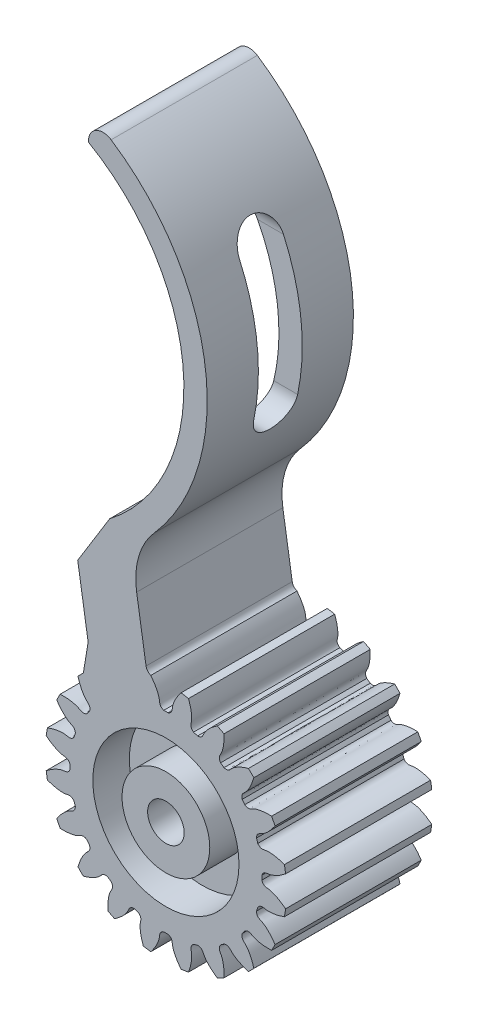
SolidWorks part; units mm, degrees
material "聚脂树脂"
ref_plane "前视基准面" through (0, 0, 0) normal (0, 0, 1) x (1, 0, 0)
ref_plane "上视基准面" through (0, 0, 0) normal (0, 1, 0) x (1, 0, 0)
ref_plane "右视基准面" through (0, 0, 0) normal (1, 0, 0) x (0, 0, -1)
other "Configuration Table"
sketch "草图1" plane through (0, 0, 0) normal (0, 0, 1) x (1, 0, 0)
  circle A0 centre (0, 0) radius 16.5
extrude "凸台-拉伸1" add sketch "草图1" along normal blind 20
ref_axis "基准轴1" through (0, 0, -1.5) along (0, 0, 1)
sketch "草图2" plane through (0, 0, 0) normal (0, 0, 1) x (1, 0, 0)
  line L0 (0, 0) -> (0, 16.5) construction
  circle A0 centre (0, 0) radius 16.5 construction
  arc A1 (0.29, 13.1218) -> (-0.29, 13.1218) centre (0, 0) ccw
  arc A2 (4.7717, 18.7474) -> (-4.7717, 18.7474) centre (0, 0) ccw
  spline S0 degree 3 poles (0.29, 13.1218) (0.9168, 13.3402) (0.8356, 13.7807) (0.9193, 14.205) (0.9283, 14.2463) (0.9395, 14.293) (0.9529, 14.3448) (0.969, 14.4018) (0.9878, 14.4638) (1.0095, 14.5309) (1.0345, 14.6028) (1.0629, 14.6795) (1.0948, 14.7608) (1.1305, 14.8467) (1.1702, 14.9371) (1.2141, 15.0317) (1.2623, 15.1305) (1.315, 15.2334) (1.3725, 15.3401) (1.4349, 15.4506) (1.5023, 15.5646) (1.575, 15.6821) (1.653, 15.8029) (1.7366, 15.9267) (1.826, 16.0534) (1.9211, 16.1829) (2.0223, 16.3149) (2.1296, 16.4493) (2.2432, 16.5859) (2.3632, 16.7244) (2.4897, 16.8646) (2.6229, 17.0065) (2.7628, 17.1496) (2.9095, 17.2939) (3.0632, 17.4391) (3.224, 17.585) (3.3918, 17.7313) (3.567, 17.8779) (3.7493, 18.0245) (3.9391, 18.1709) (4.1363, 18.3167) (4.4122, 18.5125) (4.6259, 18.6545) (4.7717, 18.7474) knots 0 0 0 0 0.165916 0.170906 0.176664 0.183189 0.190482 0.198542 0.207371 0.216967 0.22733 0.238462 0.250361 0.263027 0.276462 0.290664 0.305634 0.321371 0.337876 0.355149 0.37319 0.391998 0.411574 0.431917 0.453028 0.474907 0.497554 0.520968 0.54515 0.570099 0.595817 0.622302 0.649554 0.677575 0.706363 0.735918 0.766242 0.797333 0.829191 0.861818 0.895212 0.929373 1 1 1 1
  spline S1 degree 3 poles (-0.29, 13.1218) (-0.9168, 13.3402) (-0.8356, 13.7807) (-0.9193, 14.205) (-0.9283, 14.2463) (-0.9395, 14.293) (-0.9529, 14.3448) (-0.969, 14.4018) (-0.9878, 14.4638) (-1.0095, 14.5309) (-1.0345, 14.6028) (-1.0629, 14.6795) (-1.0948, 14.7608) (-1.1305, 14.8467) (-1.1702, 14.9371) (-1.2141, 15.0317) (-1.2623, 15.1305) (-1.315, 15.2334) (-1.3725, 15.3401) (-1.4349, 15.4506) (-1.5023, 15.5646) (-1.575, 15.6821) (-1.653, 15.8029) (-1.7366, 15.9267) (-1.826, 16.0534) (-1.9211, 16.1829) (-2.0223, 16.3149) (-2.1296, 16.4493) (-2.2432, 16.5859) (-2.3632, 16.7244) (-2.4897, 16.8646) (-2.6229, 17.0065) (-2.7628, 17.1496) (-2.9095, 17.2939) (-3.0632, 17.4391) (-3.224, 17.585) (-3.3918, 17.7313) (-3.567, 17.8779) (-3.7493, 18.0245) (-3.9391, 18.1709) (-4.1363, 18.3167) (-4.4122, 18.5125) (-4.6259, 18.6545) (-4.7717, 18.7474) knots 0 0 0 0 0.165916 0.170906 0.176664 0.183189 0.190482 0.198542 0.207371 0.216967 0.22733 0.238462 0.250361 0.263027 0.276462 0.290664 0.305634 0.321371 0.337876 0.355149 0.37319 0.391998 0.411574 0.431917 0.453028 0.474907 0.497554 0.520968 0.54515 0.570099 0.595817 0.622302 0.649554 0.677575 0.706363 0.735918 0.766242 0.797333 0.829191 0.861818 0.895212 0.929373 1 1 1 1
extrude "切除-拉伸1" cut sketch "草图2" along normal through all
pattern_circular "阵列(圆周)1" count 20 over 360 about axis through (0, 0, -1.5) along (0, 0, 1) of "切除-拉伸1"
sketch "草图3" plane through (0, 0, 0) normal (0, 0, 1) x (1, 0, 0)
  circle A0 centre (0, 0) radius 15 construction
  dimension "Dn" = 30
sketch "草图4" plane through (0, 0, 20) normal (0, 0, 1) x (1, 0, 0)
  line L0 (0, 0) -> (0, 24.252) construction
  line L1 (0, 0) -> (-4.1504, 26.2048) construction
  line L2 (-14.6667, -3.2847) -> (-22.6322, 47.0071) construction
  line L3 (-12.7072, 29.0903) -> (-7.9015, -1.2515)
  line L4 (-4.8057, 30.3418) -> (0, 0)
  line L5 (-11.2693, 79.2123) -> (-10.5853, 75.2708)
  line L6 (-11.294, 12.029) -> (-10.6385, 16.029)
  line L7 (-3.0932, 16.2075) -> (-2.5812, 16.2969)
  line L8 (0, 0) -> (-34.8237, -5.5155) construction
  line L9 (-7.9015, -1.2515) -> (0, 0)
  circle A0 centre (0, 0) radius 12.5 construction
  circle A1 centre (-23.5381, 52.727) radius 29.189 construction
  arc A2 (-2.0665, 16.3701) -> (-3.0932, 16.2075) centre (0, 0) ccw construction
  arc A3 (-4.8057, 30.3418) -> (-11.2693, 79.2123) centre (-23.5381, 52.727) ccw
  circle A4 centre (-23.5381, 52.727) radius 26 construction
  arc A6 (-12.7072, 29.0903) -> (-10.5853, 75.2708) centre (-23.5381, 52.727) ccw
  arc A8 (-3.7791, 12.5692) -> (-4.3306, 12.39) centre (0, 0) ccw construction
  arc A9 (-7.024, 14.9303) -> (-7.9502, 14.4584) centre (0, 0) ccw construction
  arc A10 (-7.4782, 10.7862) -> (-7.9474, 10.4453) centre (0, 0) ccw construction
  arc A12 (-3.7791, 12.5692) -> (-4.3306, 12.39) centre (0, 0) ccw
  arc A13 (-7.024, 14.9303) -> (-7.9502, 14.4584) centre (0, 0) ccw
  arc A14 (-7.4782, 10.7862) -> (-7.9474, 10.4453) centre (0, 0) ccw
  spline S0 degree 3 poles (2295.3671, 1929.7263) (-117.6975, -134.774) (-40.8912, 20.8175) (-11.0168, 11.9483) (-10.7713, 11.8675) (-10.4966, 11.7648) (-10.2471, 11.6599) (-10.0224, 11.5547) (-9.822, 11.4509) (-9.671, 11.3649) (-9.5386, 11.2841) (-9.4441, 11.2225) (-9.3578, 11.1623) (-9.3008, 11.1209) (-9.2491, 11.0817) (-9.2026, 11.0451) (-9.1503, 11.0021) (-9.105, 10.9626) (-4.5559, 6.7443) (-24.7562, -23.4769) (1867.2073, 2351.7135) knots -12.160638 -12.160638 -12.160638 -12.160638 0.502446 0.525093 0.568083 0.608002 0.644851 0.678629 0.709336 0.736973 0.749639 0.77267 0.783033 0.792629 0.801458 0.809518 0.816811 0.829094 0.834084 3.350793 3.350793 3.350793 3.350793 only from (-11.294, 12.029) to (-7.9474, 10.4453) construction
  spline S1 degree 3 poles (-3000.2151, -128.3054) (33.5455, 6.2288) (-2.7783, 7.6499) (-3.5171, 13.8097) (-3.5224, 13.8696) (-3.5265, 13.9372) (-3.5289, 13.9963) (-3.5307, 14.0865) (-3.5293, 14.2134) (-3.5206, 14.3824) (-3.5033, 14.5733) (-3.4754, 14.7858) (-3.4352, 15.0192) (-3.381, 15.2729) (-3.3111, 15.5461) (-3.2398, 15.7847) (-3.1737, 15.9845) (7.1936, 45.3178) (178.2143, 16.0013) (-2910.3372, -722.7198) knots -2.350827 -2.350827 -2.350827 -2.350827 0.165916 0.170906 0.183189 0.190482 0.198542 0.207371 0.22733 0.250361 0.276462 0.305634 0.337876 0.37319 0.411574 0.453028 0.474907 0.497554 13.160601 13.160601 13.160601 13.160601 only from (-3.7791, 12.5692) to (-3.0932, 16.2075) construction
  spline S2 degree 3 poles (2779.3421, 1125.9713) (-153.5845, -91.8071) (-32.4569, 32.4347) (-6.7853, 14.7679) (-6.5768, 14.6152) (-6.3474, 14.4326) (-6.1425, 14.2557) (-5.9612, 14.0862) (-5.8028, 13.9257) (-5.6857, 13.7971) (-5.5848, 13.6794) (-5.514, 13.5916) (-5.4504, 13.5077) (-5.409, 13.4507) (-5.3719, 13.3975) (-5.3391, 13.3482) (-5.3027, 13.2912) (-5.2717, 13.2396) (-2.2488, 7.822) (-30.7993, -14.6778) (2502.5391, 1659.6136) knots -12.160638 -12.160638 -12.160638 -12.160638 0.502446 0.525093 0.568083 0.608002 0.644851 0.678629 0.709336 0.736973 0.749639 0.77267 0.783033 0.792629 0.801458 0.809518 0.816811 0.829094 0.834084 3.350793 3.350793 3.350793 3.350793 only from (-7.024, 14.9303) to (-4.3306, 12.39) construction
  spline S3 degree 3 poles (-2813.7256, -1049.1431) (29.9789, 16.29) (-5.0063, 6.4169) (-7.6124, 12.047) (-7.636, 12.1023) (-7.6607, 12.1653) (-7.6812, 12.2208) (-7.7108, 12.3061) (-7.7487, 12.4272) (-7.7927, 12.5905) (-7.8352, 12.7775) (-7.8743, 12.9882) (-7.9082, 13.2226) (-7.9351, 13.4806) (-7.9531, 13.762) (-7.959, 14.011) (-7.9578, 14.2215) (-7.1625, 45.3227) (164.5472, 70.2894) (-2544.5625, -1586.6911) knots -2.350827 -2.350827 -2.350827 -2.350827 0.165916 0.170906 0.183189 0.190482 0.198542 0.207371 0.22733 0.250361 0.276462 0.305634 0.337876 0.37319 0.411574 0.453028 0.474907 0.497554 13.160601 13.160601 13.160601 13.160601 only from (-7.4782, 10.7862) to (-7.9502, 14.4584) construction
  spline S4 degree 3 poles (-3.7791, 12.5692) (-3.2504, 12.9706) (-3.4637, 13.3644) (-3.5171, 13.8097) (-3.5224, 13.8696) (-3.5265, 13.9372) (-3.5289, 13.9963) (-3.5307, 14.0865) (-3.5293, 14.2134) (-3.5206, 14.3824) (-3.5033, 14.5733) (-3.4754, 14.7858) (-3.4352, 15.0192) (-3.381, 15.2729) (-3.3111, 15.5461) (-3.224, 15.8378) (-3.1479, 16.0599) (-3.1017, 16.1848) (-3.0932, 16.2075) knots 0 0 0 0 0.165916 0.170906 0.183189 0.190482 0.198542 0.207371 0.22733 0.250361 0.276462 0.305634 0.337876 0.37319 0.411574 0.453028 0.497554 0.507432 0.507432 0.507432 0.507432
  spline S5 degree 3 poles (-7.024, 14.9303) (-6.9129, 14.8568) (-6.7202, 14.7228) (-6.459, 14.5233) (-6.2419, 14.3433) (-6.0489, 14.1699) (-5.8792, 14.0047) (-5.7318, 13.8492) (-5.6234, 13.7255) (-5.5309, 13.613) (-5.4664, 13.5298) (-5.409, 13.4507) (-5.3719, 13.3975) (-5.3391, 13.3482) (-5.3027, 13.2912) (-5.2717, 13.2396) (-5.0532, 12.848) (-4.9943, 12.404) (-4.3306, 12.39) knots 0.492568 0.492568 0.492568 0.492568 0.546972 0.588426 0.62681 0.662124 0.694366 0.723538 0.749639 0.761538 0.783033 0.792629 0.801458 0.809518 0.816811 0.829094 0.834084 1 1 1 1
  spline S6 degree 3 poles (-7.4782, 10.7862) (-7.0995, 11.3313) (-7.424, 11.64) (-7.6124, 12.047) (-7.636, 12.1023) (-7.6607, 12.1653) (-7.6812, 12.2208) (-7.7108, 12.3061) (-7.7487, 12.4272) (-7.7927, 12.5905) (-7.8352, 12.7775) (-7.8743, 12.9882) (-7.9082, 13.2226) (-7.9351, 13.4806) (-7.9531, 13.762) (-7.9603, 14.0664) (-7.9566, 14.3011) (-7.9513, 14.4342) (-7.9502, 14.4584) knots 0 0 0 0 0.165916 0.170906 0.183189 0.190482 0.198542 0.207371 0.22733 0.250361 0.276462 0.305634 0.337876 0.37319 0.411574 0.453028 0.497554 0.507432 0.507432 0.507432 0.507432
  spline S7 degree 3 poles (-11.294, 12.029) (-11.1656, 11.9934) (-10.9409, 11.9255) (-10.6308, 11.8165) (-10.3687, 11.7125) (-10.1316, 11.6072) (-9.9192, 11.5025) (-9.7309, 11.4002) (-9.5896, 11.316) (-9.4669, 11.2376) (-9.3798, 11.1783) (-9.3008, 11.1209) (-9.2491, 11.0817) (-9.2026, 11.0451) (-9.1503, 11.0021) (-9.105, 10.9626) (-8.7761, 10.6576) (-8.5829, 10.2536) (-7.9474, 10.4453) knots 0.492568 0.492568 0.492568 0.492568 0.546972 0.588426 0.62681 0.662124 0.694366 0.723538 0.749639 0.761538 0.783033 0.792629 0.801458 0.809518 0.816811 0.829094 0.834084 1 1 1 1
  dimension "D6" = 52
  dimension "D7" = 76
  dimension "D5" = 30.72
  dimension "D10" = 25
  dimension "D9" = 80
  dimension "D1" = 9
  dimension "D2" = 15
  dimension "D3" = 8
  dimension "D4" = 30.72
  dimension "D8" = 4
extrude "凸台-拉伸2" add sketch "草图4" against normal blind 20 contours S7 A14 S6 A13 S5 A12 S4 L7 A6 | S7 region at (3.146, 51.5009, 20) region at (-10.6183, 13.2048, 20)
fillet "圆角1" radius 1 1 edges
fillet "圆角2" radius 2 1 edges at (-11.2693, 79.2123, 10)
fillet "圆角4" radius 10 1 edges at (-4.8057, 30.3418, 10)
sketch "草图5" plane through (0, 0, 20) normal (0, 0, 1) x (1, 0, 0)
  circle A0 centre (0, 0) radius 2.5
  dimension "D1" = 5
extrude "切除-拉伸2" cut sketch "草图5" against normal blind 20
chamfer "倒角1" distance 5 angle 45 1 edges at (-12.7072, 29.0903, 10) first distance on face at (-11.6728, 22.5596, 10)
sketch "草图7" plane through (0, 0, 0) normal (0, 0, -1) x (-1, 0, 0)
  circle A0 centre (0, 0) radius 10
  dimension "D1" = 20
extrude "切除-拉伸3" cut sketch "草图7" against normal blind 3
sketch "草图8" plane through (0, 0, 20) normal (0, 0, 1) x (1, 0, 0)
  circle A0 centre (0, 0) radius 6
  circle A1 centre (0, 0) radius 10
  dimension "D1" = 12
  dimension "D2" = 20
extrude "切除-拉伸4" cut sketch "草图8" against normal blind 5
sketch "草图9" plane through (0, 0, 0) normal (1, 0, 0) x (0, 0, -1)
  line L0 (-10, 46.7) -> (-10, 64.7) construction
  line L5 (-13, 46.7) -> (-13, 64.7)
  line L6 (-7, 46.7) -> (-7, 64.7)
  line L7 (0, 33.4384) -> (0, 77.1105) construction
  arc A0 (-13, 46.7) -> (-7, 46.7) centre (-10, 46.7) ccw
  arc A1 (-7, 64.7) -> (-13, 64.7) centre (-10, 64.7) ccw
  point P2 (-10, 55.7)
  dimension "D2" = 3
  dimension "D1" = 18
  dimension "D3" = 10
  dimension "D4" = 55.7
extrude "切除-拉伸5" cut sketch "草图9" along normal blind 10 and the other way blind 10
